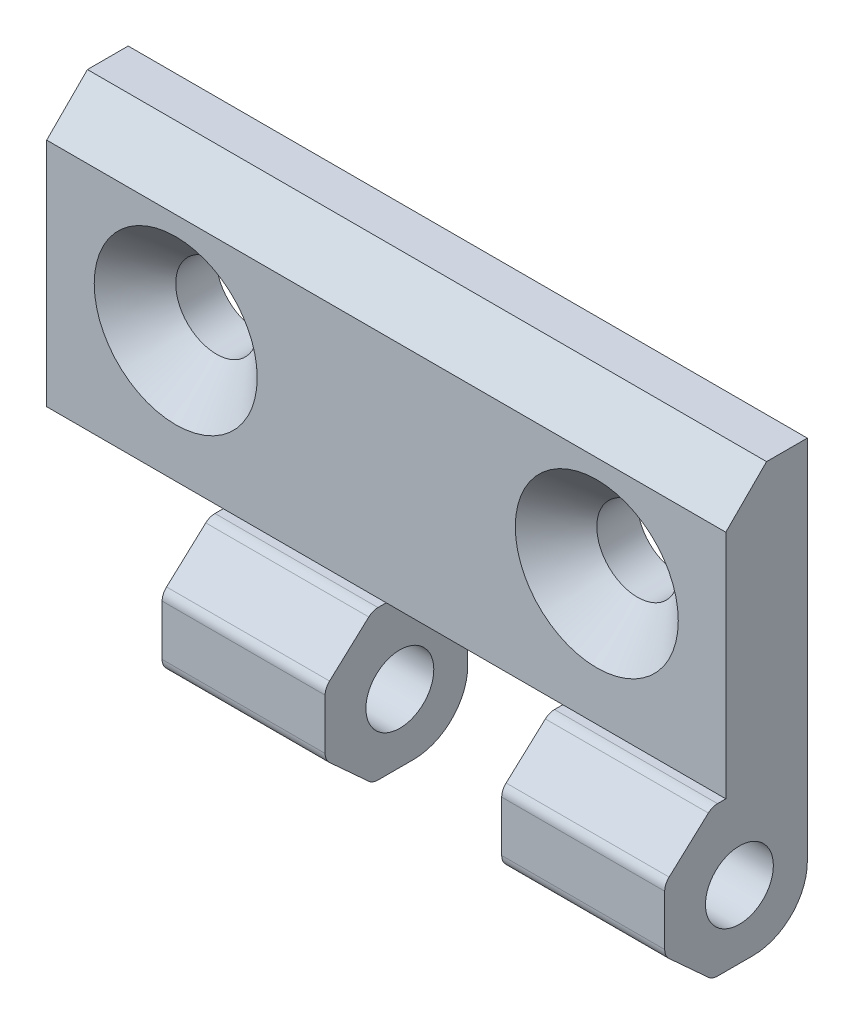
SolidWorks part; units mm, degrees
ref_plane "Front Plane" through (0, 0, 0) normal (1, 0, 0) x (0, 1, 0)
ref_plane "Top Plane" through (0, 0, 0) normal (0, 0, 1) x (0, 1, 0)
ref_plane "Right Plane" through (0, 0, 0) normal (0, 1, 0) x (-1, 0, 0)
sketch "Sketch1" plane through (0, 0, 0) normal (0, 0, 1) x (0, 1, 0)
  line L1 (-10, -25) -> (10, -25)
  line L2 (-10, -25) -> (-10, 25)
  line L3 (-10, 25) -> (10, 25)
  line L4 (10, -25) -> (10, 25)
  line L5 (-10, -25) -> (10, 25) construction
  line L6 (-10, 25) -> (10, -25) construction
  point P0 (0, 0)
  dimension "D1" = 50
  dimension "D2" = 20
extrude "Boss-Extrude1" add sketch "Sketch1" along normal blind 6
sketch "Sketch2" plane through (25, 0, 0) normal (1, 0, 0) x (0, 1, 0)
  line L0 (-10, 0) -> (-17, 0)
  line L1 (-21, 4) -> (-21, 6.6118)
  line L2 (-17.3593, 10.5) -> (-13.6407, 10.5)
  line L3 (-10, 6.6118) -> (-10, 6)
  line L4 (-10, 6) -> (10, 6) construction
  line L5 (10, 6) -> (10, 0) construction
  line L6 (-10.262, 7.2865) -> (-12.9026, 10.1748)
  line L8 (-20.738, 7.2865) -> (-18.0974, 10.1748)
  line L9 (-10, 6) -> (-10, 0)
  line L11 (-10, 0) -> (10, 0) construction
  arc A0 (-21, 4) -> (-17, 0) centre (-17, 4) ccw
  circle A1 centre (-16, 5) radius 2.5
  arc A2 (-10.262, 7.2865) -> (-10, 6.6118) centre (-11, 6.6118) cw
  arc A3 (-20.738, 7.2865) -> (-21, 6.6118) centre (-20, 6.6118) ccw
  arc A4 (-12.9026, 10.1748) -> (-13.6407, 10.5) centre (-13.6407, 9.5) ccw
  arc A5 (-18.0974, 10.1748) -> (-17.3593, 10.5) centre (-17.3593, 9.5) cw
  point P6 (-10, 7)
  point P25 (-21, 7)
  point P28 (-13.2, 10.5)
  point P31 (-17.8, 10.5)
  dimension "D3" = 5
  dimension "D5" = 4
  dimension "D7" = 1
  dimension "D1" = 4.5
  dimension "D2" = 31
  dimension "D4" = 3.2
  dimension "D6" = 1
  dimension "D8" = 2.5
  dimension "D9" = 2.5
extrude "Boss-Extrude2" add sketch "Sketch2" against normal blind 12 separate body
pattern_linear "LPattern1" count 2 spacing 25 along (-1, 0, 0) of "Boss-Extrude2"
combine bodies "Combine1" operation type add bodies to combine 102 103 101
sketch "Sketch3" plane through (0, 0, 6) normal (0, 0, 1) x (1, 0, 0)
  line L0 (25, -10) -> (25, 10) construction
  line L1 (25, 10) -> (-25, 10) construction
  line L2 (0, 10) -> (0, -2.5535) construction
  circle A0 centre (15.5, -0.4) radius 3
  circle A1 centre (-15.5, -0.4) radius 3
  dimension "D1" = 6
  dimension "D2" = 9.5
  dimension "D3" = 10.4
extrude "Cut-Extrude1" cut sketch "Sketch3" against normal through all
chamfer "Chamfer1" distance 3 angle 45 2 edges at (-18.5, -0.4, 6) (18.5, -0.4, 6)
chamfer "Chamfer2" distance 3 angle 45 1 edges at (0, 10, 6)
equation "\"D2@Sketch2\"=11+\"D2@Sketch1\""
